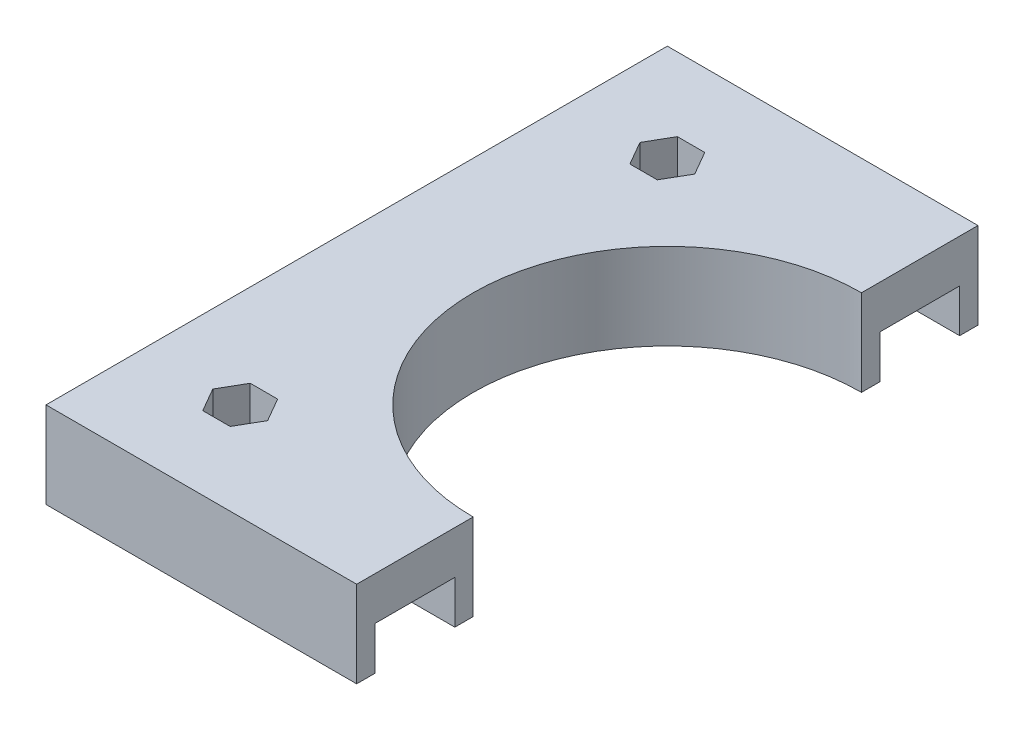
SolidWorks part; units mm, degrees
ref_plane "Front Plane" through (0, 0, 0) normal (0, 0, 1) x (1, 0, 0)
ref_plane "Top Plane" through (0, 0, 0) normal (0, 1, 0) x (1, 0, 0)
ref_plane "Right Plane" through (0, 0, 0) normal (1, 0, 0) x (0, 0, -1)
sketch "Sketch1" plane through (0, 0, 0) normal (0, 1, 0) x (1, 0, 0)
  line L0 (0, 74.1448) -> (0, -72.8187)
  line L1 (-36, -36) -> (36, -36)
  line L2 (-36, -36) -> (-36, 36)
  line L3 (-36, 36) -> (36, 36)
  line L4 (36, -36) -> (36, 36)
  line L5 (-36, -36) -> (36, 36) construction
  line L6 (-36, 36) -> (36, -36) construction
  circle A0 centre (0, 0) radius 22.5
  circle A1 centre (-24.7487, 24.7487) radius 1.5
  circle A2 centre (24.7487, 24.7487) radius 1.5
  circle A3 centre (24.7487, -24.7487) radius 1.5
  circle A4 centre (-24.7487, -24.7487) radius 1.5
  point P0 (0, 0)
  point P21 (0, 0)
  dimension "D1" = 45
  dimension "D5" = 3
  dimension "D2" = 36
  dimension "D3" = 36
  dimension "D4" = 0
  dimension "D7" = 35
  dimension "D8" = 0
  dimension "D6" = 4
extrude "Boss-Extrude1" add sketch "Sketch1" along normal blind 5 and the other way blind 5 contours A0 L0 L3 L2 L1 region at (-0.805, 0, -29.25)
sketch "Sketch2" plane through (0, 5, 0) normal (0, 1, 0) x (1, 0, 0)
  line L0 (-36, 36) -> (0, 36) construction
  line L1 (-23.161, 27.4987) -> (-26.3365, 27.4987)
  line L2 (-26.3365, 27.4987) -> (-27.9242, 24.7487)
  line L3 (-27.9242, 24.7487) -> (-26.3365, 21.9987)
  line L4 (-26.3365, 21.9987) -> (-23.161, 21.9987)
  line L5 (-23.161, 21.9987) -> (-21.5733, 24.7487)
  line L6 (-21.5733, 24.7487) -> (-23.161, 27.4987)
  circle A0 centre (-24.7487, 24.7487) radius 2.75 construction
  dimension "D1" = 5.5
  dimension "D2" = 0
extrude "Cut-Extrude1" cut sketch "Sketch2" against normal blind 5
mirror "Mirror1" about plane through (0, 0, 0) normal (0, 0, 1) of "Cut-Extrude1"
sketch "Sketch4" plane through (0, -5, 0) normal (0, -1, 0) x (1, 0, 0)
  line L0 (0, -36) -> (0, -22.5) construction
  line L1 (0, -24.625) -> (-9.4543, -24.625)
  line L2 (0, -24.625) -> (0, -33.875)
  line L3 (0, -33.875) -> (-9.4543, -33.875)
  line L4 (-9.4543, -24.625) -> (-9.4543, -33.875)
  line L5 (-36, -36) -> (0, -36) construction
  dimension "D1" = 9.25
  dimension "D2" = 2.125
extrude "Cut-Extrude2" cut sketch "Sketch4" against normal blind 5
mirror "Mirror3" about plane through (0, 0, 0) normal (0, 0, 1) of "Cut-Extrude2"
